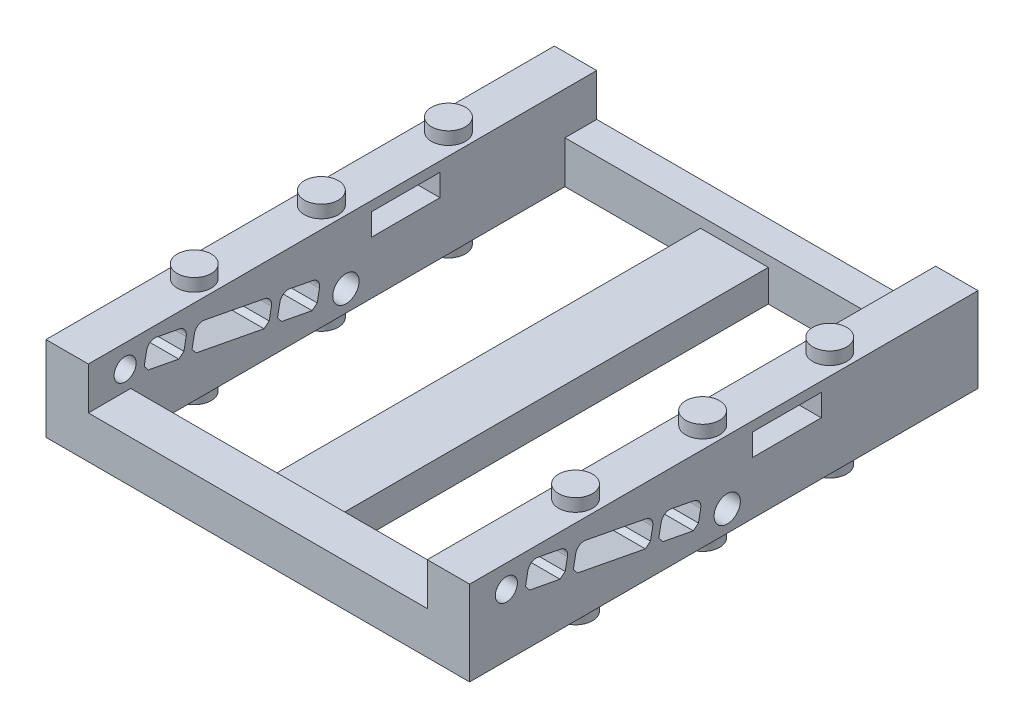
SolidWorks part; units mm, degrees
material "PAHT-CF"
ref_plane "Front Plane" through (0, 0, 0) normal (0, 0, 1) x (1, 0, 0)
ref_plane "Top Plane" through (0, 0, 0) normal (0, 1, 0) x (1, 0, 0)
ref_plane "Right Plane" through (0, 0, 0) normal (1, 0, 0) x (0, 0, -1)
sketch "Sketch1" plane through (0, 0, 0) normal (0, 1, 0) x (1, 0, 0)
  line L0 (-40, 60) -> (-40, -60)
  line L1 (-50, -60) -> (50, -60) construction
  line L2 (-50, -60) -> (-50, 60)
  line L3 (-50, 60) -> (50, 60) construction
  line L4 (50, -60) -> (50, 60)
  line L5 (-50, -60) -> (-41.6667, -50) construction
  line L6 (-50, 60) -> (10.4167, -12.5) construction
  line L7 (40, 60) -> (40, -60)
  line L8 (40, -60) -> (50, -60)
  line L9 (-50, 60) -> (-40, 60)
  line L10 (40, 60) -> (50, 60)
  line L11 (-50, -60) -> (-40, -60)
  line L12 (-40, 0) -> (40, 0) construction
  line L13 (-40, 60) -> (40, 60)
  line L14 (-40, 60) -> (-40, 52.5)
  line L15 (-40, 52.5) -> (40, 52.5)
  line L16 (40, 60) -> (40, 52.5)
  line L17 (-40, -50) -> (40, -50)
  line L18 (-40, -50) -> (-40, -60)
  line L19 (-40, -60) -> (40, -60)
  line L20 (40, -50) -> (40, -60)
  line L21 (-18.75, -22.5) -> (0, 0) construction
  line L23 (-40, 20) -> (-40, 10)
  line L25 (40, 20) -> (40, 10)
  line L27 (-40, -12.5) -> (-40, -22.5)
  line L29 (40, -12.5) -> (40, -22.5)
  line L30 (18.75, -22.5) -> (50, -60) construction
  line L32 (16.6667, 20) -> (50, 60) construction
  point P0 (0, 0)
  point P21 (0, 0)
  dimension "D1" = 120
  dimension "D2" = 100
  dimension "D3" = 10
  dimension "D4" = 10
  dimension "D5" = 52.5
  dimension "D6" = 50
  dimension "D7" = 10
  dimension "D8" = 7.5
  dimension "D10" = 10
extrude "Boss-Extrude1" add sketch "Sketch1" along normal blind 20 contours L2 L11 L0 L9 | L0 L19 L7 L17 | L0 L15 L7 L13 | L10 L7 L8 L4
sketch "Sketch4" [suppressed] plane through (0, 0, 60) normal (0, 0, 1) x (1, 0, 0)
  line L0 (40, 20) -> (40, 0) construction
  line L1 (-40, 20) -> (40, 20)
  line L2 (-40, 20) -> (-40, 17.5)
  line L3 (-40, 17.5) -> (40, 17.5)
  line L4 (40, 20) -> (40, 17.5)
  line L5 (40, 20) -> (40, 0) construction
  line L6 (-40, 0) -> (40, 0)
  line L7 (-40, 0) -> (-40, 2.5)
  line L8 (-40, 2.5) -> (40, 2.5)
  line L9 (40, 0) -> (40, 2.5)
  line L10 (-40, 20) -> (-40, 0) construction
  line L11 (-40, 11) -> (40, 11)
  line L12 (-40, 11) -> (-40, 8.5)
  line L13 (-40, 8.5) -> (40, 8.5)
  line L14 (40, 11) -> (40, 8.5)
  dimension "D1" = 2.5
  dimension "D2" = 2.5
  dimension "D3" = 2.5
  dimension "D4" = 6
extrude "Cut-Extrude2" [suppressed] cut sketch "Sketch4" against normal up to surface (120 mm away)
sketch "Sketch2" plane through (0, 20, 0) normal (0, 1, 0) x (1, 0, 0)
  line L0 (-45, 60) -> (-45, -60) construction
  line L1 (-50, 60) -> (-40, 60)
  line L2 (-50, 60) -> (-50, -60)
  line L3 (-50, -60) -> (-40, -60)
  line L4 (-40, 60) -> (-40, -60)
  line L5 (-50, -60) -> (50, -60) construction
  line L6 (-40, -50) -> (-40, -60)
  circle A0 centre (-45, 30) radius 4
  circle A1 centre (-45, 0) radius 4
  circle A2 centre (-45, -30) radius 4
  point P14 (-39.3198, -60)
  dimension "D1" = 8
  dimension "D2" = 8
  dimension "D3" = 8
  dimension "D4" = 30
  dimension "D5" = 30
  dimension "D6" = 30
extrude "Boss-Extrude2" add sketch "Sketch2" along normal blind 3 contours A2 L0 | L0 A2 | L0 A1 | A1 L0 | L0 A0 | A0 L0 region at (-43.3023, 20, -30) region at (-46.6977, 20, -30) region at (-43.3023, 20, 0) region at (-46.6977, 20, 0) region at (-46.6977, 20, 30) region at (-43.3023, 20, 30)
mirror "Mirror1" about plane through (0, 0, 0) normal (1, 0, 0) of "Boss-Extrude2"
ref_plane "Plane1" through (0, 10, 0) normal (0, 1, 0) x (1, 0, 0)
mirror "Mirror2" about plane through (0, 10, 0) normal (0, 1, 0) of "Mirror1", "Boss-Extrude2"
sketch "Sketch3" plane through (-50, 0, 0) normal (-1, 0, 0) x (0, 0, 1)
  line L5 (-0.7983, 10) -> (52, 14.6193)
  line L7 (-0.7983, 20) -> (-0.7983, 0) construction
  line L8 (60, 20) -> (-60, 20) construction
  line L9 (-60, 0) -> (60, 0)
  line L11 (60, 0) -> (60, 20)
  line L12 (60, 20) -> (-60, 20)
  line L13 (-60, 20) -> (-60, 0)
  line L14 (-60, 0) -> (60, 0)
  line L15 (60, 0) -> (60, 20)
  line L16 (60, 20) -> (-52.8464, 20)
  line L18 (60, 20) -> (-60, 20)
  line L19 (-0.7983, 10) -> (60, 10)
  line L20 (52, 14.6193) -> (51.9651, 15.0177)
  circle A1 centre (-0.7983, 10) radius 3.1
  circle A2 centre (-0.7983, 10) radius 53
  circle A3 centre (51.9651, 15.0177) radius 2.6
  dimension "D1" = 5.2
  dimension "D2" = 6.2
  dimension "D4" = 8
  dimension "D3" = 0
  dimension "D6" = 5
  dimension "D5" = 106
  dimension "D7" = 0.4
extrude "Cut-Extrude1" [suppressed] cut sketch "Sketch3" against normal blind 5.2 contours A1 | A3
mirror "Mirror3" [suppressed] about plane through (0, 0, 0) normal (1, 0, 0)
sketch "Sketch8" plane through (0, 0, 60) normal (0, 0, 1) x (1, 0, 0)
  line L1 (-50, 20) -> (50, 20) construction
  line L17 (-40, 20) -> (40, 20)
  line L18 (-40, 20) -> (-40, 10)
  line L19 (-40, 10) -> (40, 10)
  line L20 (40, 20) -> (40, 10)
  line L21 (-50, 20) -> (-50, 0) construction
  line L22 (50, 20) -> (50, 0) construction
  dimension "D1" = 10
  dimension "D2" = 10
  dimension "D3" = 10
extrude "Cut-Extrude5" cut sketch "Sketch8" against normal through all
sketch "Sketch12" plane through (-50, 0, 0) normal (-1, 0, 0) x (0, 0, 1)
  line L0 (-0.7983, 5) -> (51.327, 14.5973) construction
  line L20 (38.6538, 10.332) -> (37.4471, 11.3139)
  line L21 (37.4471, 11.3139) -> (36.9178, 14.0718)
  line L22 (43.9064, 17.4497) -> (38.5049, 16.413)
  line L23 (46.813, 12.9163) -> (46.2475, 15.8625)
  line L24 (46.813, 12.9163) -> (45.8311, 11.7096)
  line L25 (45.8311, 11.7096) -> (38.6538, 10.332)
  line L26 (35.5191, 10.7486) -> (34.9536, 13.6948)
  line L27 (35.5191, 10.7486) -> (34.5372, 9.5419)
  line L28 (18.5213, 6.4679) -> (17.3146, 7.4498)
  line L29 (18.5213, 6.4679) -> (34.5372, 9.5419)
  line L30 (17.3146, 7.4498) -> (16.7853, 10.2077)
  line L31 (18.3724, 12.5489) -> (32.6125, 15.282)
  line L32 (15.3489, 7.0809) -> (14.7834, 10.0272)
  line L33 (15.3489, 7.0809) -> (14.367, 5.8742)
  line L34 (14.367, 5.8742) -> (7.1897, 4.4967)
  line L35 (7.1897, 4.4967) -> (5.983, 5.4786)
  line L36 (12.4423, 11.6143) -> (7.0409, 10.5776)
  line L37 (5.983, 5.4786) -> (5.4537, 8.2365)
  circle A1 centre (-0.7983, 5) radius 3.1
  arc A9 (38.5049, 16.413) -> (36.9178, 14.0718) centre (38.8819, 14.4488) ccw
  arc A10 (46.2475, 15.8625) -> (43.9064, 17.4497) centre (44.2833, 15.4855) ccw
  circle A11 centre (51.327, 14.5973) radius 2.6
  arc A12 (34.9536, 13.6948) -> (32.6125, 15.282) centre (32.9895, 13.3179) ccw
  arc A13 (18.3724, 12.5489) -> (16.7853, 10.2077) centre (18.7494, 10.5847) ccw
  arc A14 (14.7834, 10.0272) -> (12.4423, 11.6143) centre (12.8193, 9.6502) ccw
  arc A15 (7.0409, 10.5776) -> (5.4537, 8.2365) centre (7.4178, 8.6135) ccw
  dimension "D2" = 6.2
  dimension "D3" = 5.2
  dimension "D1" = 16.3082
extrude "Cut-Extrude7" cut sketch "Sketch12" against normal blind 14 contours L22 A9 L21 L20 L25 L24 L23 A10 | A11 | L31 A12 L26 L27 L29 L28 L30 A13 | L36 A15 L37 L35 L34 L33 L32 A14 | A1
mirror "Mirror5" about plane through (0, 0, 0) normal (1, 0, 0) of "Cut-Extrude7"
sketch "Sketch6" [suppressed] plane through (-50, 0, 0) normal (-1, 0, 0) x (0, 0, 1)
  line L0 (-0.7983, 10) -> (51.9651, 15.0177) construction
  line L1 (17.9482, 10.0156) -> (10.6864, 9.2697)
  line L2 (10.6864, 9.2697) -> (9.5895, 10.1623)
  line L3 (9.5895, 10.1623) -> (9.3034, 12.9476)
  line L4 (18.8408, 11.1126) -> (17.9482, 10.0156)
  line L5 (18.5547, 13.8979) -> (18.8408, 11.1126)
  line L6 (11.0885, 15.1415) -> (16.3608, 15.6831)
  line L7 (34.479, 12.5179) -> (35.576, 11.6253)
  line L8 (42.8378, 12.3712) -> (43.7304, 13.4682)
  line L9 (35.576, 11.6253) -> (42.8378, 12.3712)
  line L10 (43.7304, 13.4682) -> (43.4443, 16.2535)
  line L11 (41.2504, 18.0387) -> (35.9781, 17.4971)
  line L12 (34.1929, 15.3032) -> (34.479, 12.5179)
  line L13 (23.2511, 10.2588) -> (22.1542, 11.1514)
  line L14 (21.8476, 14.1357) -> (22.1542, 11.1514)
  line L15 (28.7061, 16.8507) -> (23.6328, 16.3295)
  line L16 (31.2065, 12.0812) -> (30.9, 15.0655)
  line L17 (31.2065, 12.0812) -> (30.314, 10.9843)
  line L18 (23.2511, 10.2588) -> (30.314, 10.9843)
  arc A0 (18.5547, 13.8979) -> (16.3608, 15.6831) centre (16.5652, 13.6936) ccw
  arc A1 (11.0885, 15.1415) -> (9.3034, 12.9476) centre (11.2929, 13.152) ccw
  arc A2 (43.4443, 16.2535) -> (41.2504, 18.0387) centre (41.4547, 16.0492) ccw
  arc A3 (35.9781, 17.4971) -> (34.1929, 15.3032) centre (36.1825, 15.5076) ccw
  arc A4 (23.6328, 16.3295) -> (21.8476, 14.1357) centre (23.8372, 14.34) ccw
  arc A5 (30.9, 15.0655) -> (28.7061, 16.8507) centre (28.9105, 14.8611) ccw
  circle A6 centre (-0.7983, 10) radius 3.1 construction
  circle A7 centre (51.9651, 15.0177) radius 2.6 construction
  dimension "D1" = 0.8219
  dimension "D2" = 0.7517
  dimension "D3" = 1.0268
  dimension "D4" = 3.3
  dimension "D5" = 3.3
  dimension "D6" = 0.9581
  dimension "D7" = 0.8332
  dimension "D8" = 0.763
extrude "Cut-Extrude3" [suppressed] cut sketch "Sketch6" against normal blind 10
mirror "Mirror4" [suppressed] about plane through (0, 0, 0) normal (1, 0, 0)
sketch "Sketch13" plane through (50, 0, 0) normal (1, 0, 0) x (0, 0, -1)
  line L0 (-60, 20) -> (-60, 0) construction
  line L1 (-10, 18) -> (35, 18)
  line L2 (-10, 18) -> (-10, 15)
  line L3 (-10, 15) -> (35, 15)
  line L4 (35, 18) -> (35, 15)
  line L5 (60, 20) -> (60, 0) construction
  line L6 (-60, 0) -> (60, 0) construction
  point P10 (0, 0)
  dimension "D1" = 50
  dimension "D2" = 25
  dimension "D3" = 3
  dimension "D4" = 15
extrude "Boss-Extrude3" [suppressed] add sketch "Sketch13" against normal up to surface (90 mm away)
fillet "Fillet1" [suppressed] radius 3
sketch "Sketch14" plane through (0, 0, -52.5) normal (0, 0, 1) x (1, 0, 0)
  line L0 (-40, 15) -> (40, 15) construction
  line L1 (-40, 20) -> (-40, 10) construction
  line L2 (40, 20) -> (40, 10) construction
  circle A0 centre (-25, 15) radius 3
  circle A1 centre (0, 15) radius 3
  circle A2 centre (25, 15) radius 3
  dimension "D1" = 6
  dimension "D2" = 6
  dimension "D3" = 6
  dimension "D4" = 15
  dimension "D5" = 15
  dimension "D6" = 25
extrude "Cut-Extrude8" [suppressed] cut sketch "Sketch14" against normal through all
sketch "Sketch15" plane through (0, 0, 50) normal (0, 0, -1) x (-1, 0, 0)
  line L0 (-8, 0) -> (8, 0)
  line L1 (50, 0) -> (-50, 0) construction
  line L3 (-8, 0) -> (8, 0)
  line L4 (-8, 0) -> (-8, 7.5)
  line L5 (-8, 7.5) -> (8, 7.5)
  line L6 (8, 0) -> (8, 7.5)
  point P6 (0, 0)
  line M5 (-40, 0) -> (40, 0)
  dimension "D1" = 16
  dimension "D2" = 7.5
extrude "Boss-Extrude4" add sketch "Sketch15" along normal up to surface (102.5 mm away) contours L6 L5 L4 M5 region at (0, 3.75, 50) up to face at (0, 5, -52.5)
sketch "Sketch16" plane through (0, 0, 60) normal (0, 0, 1) x (1, 0, 0)
  line L2 (-8.1, 10) -> (8.1, 10)
  line L13 (-40, 10) -> (40, 10) construction
  line L14 (0, 0) -> (0, 10)
  line L16 (-8.1, 10) -> (8.1, 10)
  line L17 (-8.1, 10) -> (-8.1, 13)
  line L18 (-8.1, 13) -> (8.1, 13)
  line L19 (8.1, 10) -> (8.1, 13)
  line L20 (-8.1, 13) -> (8.1, 13)
  line L21 (-8.1, 13) -> (-8.1, 18.2)
  line L22 (-8.1, 18.2) -> (8.1, 18.2)
  line L23 (8.1, 13) -> (8.1, 18.2)
  point P6 (0, 10)
  dimension "D1" = 16.2
  dimension "D2" = 5.2
  dimension "D3" = 3
extrude "Cut-Extrude9" [suppressed] cut sketch "Sketch16" against normal through all contours L21 L20 L23 L22
sketch "Sketch17" [suppressed] plane through (0, 0, 60) normal (0, 0, 1) x (1, 0, 0)
  line L10 (-40, 10) -> (40, 10) construction
  line L18 (-8.1, 13) -> (8.1, 13)
  line L19 (-8.1, 13) -> (-8.1, 10)
  line L20 (-8.1, 10) -> (8.1, 10)
  line L21 (8.1, 13) -> (8.1, 10)
  line L22 (-40, 20) -> (40, 20) construction
  line L23 (8.1, 10) -> (11.1, 10)
  line L24 (8.1, 10) -> (8.1, 20)
  line L25 (8.1, 20) -> (11.1, 20)
  line L26 (11.1, 10) -> (11.1, 20)
  line L28 (-8.1, 10) -> (-11.1, 10)
  line L29 (-8.1, 10) -> (-8.1, 20)
  line L30 (-8.1, 20) -> (-11.1, 20)
  line L31 (-11.1, 10) -> (-11.1, 20)
  line L32 (-8.1, 20) -> (8.1, 20)
  line L33 (-8.1, 20) -> (-8.1, 18.2)
  line L34 (-8.1, 18.2) -> (8.1, 18.2)
  line L35 (8.1, 20) -> (8.1, 18.2)
  line M23 (40, 10) -> (-40, 10)
  dimension "D1" = 3
  dimension "D2" = 3
extrude "Boss-Extrude5" [suppressed] add sketch "Sketch17" against normal blind 6 contours L21 L18 L19 M23 | L31 L19 L29 L30 M23 | L29 L34 L24 L32 | L26 L25 L24 L21 M23
sketch "Sketch18" plane through (50, 0, 0) normal (1, 0, 0) x (0, 0, -1)
  line L0 (0, 0) -> (23, 0)
  line L1 (-4, 0) -> (4, 0) construction
  line L2 (-60, 0) -> (60, 0) construction
  line L3 (23, 0) -> (23, 12.5)
  line L5 (23, 12.5) -> (6.8, 12.5)
  line L6 (23, 12.5) -> (23, 17.7)
  line L7 (23, 17.7) -> (6.8, 17.7)
  line L8 (6.8, 12.5) -> (6.8, 17.7)
  dimension "D1" = 16.2
  dimension "D2" = 5.2
  dimension "D3" = 12.5
  dimension "D4" = 23
extrude "Cut-Extrude10" cut sketch "Sketch18" against normal through all contours L8 L5 L6 L7 region at (50, 15.1, -14.9)
